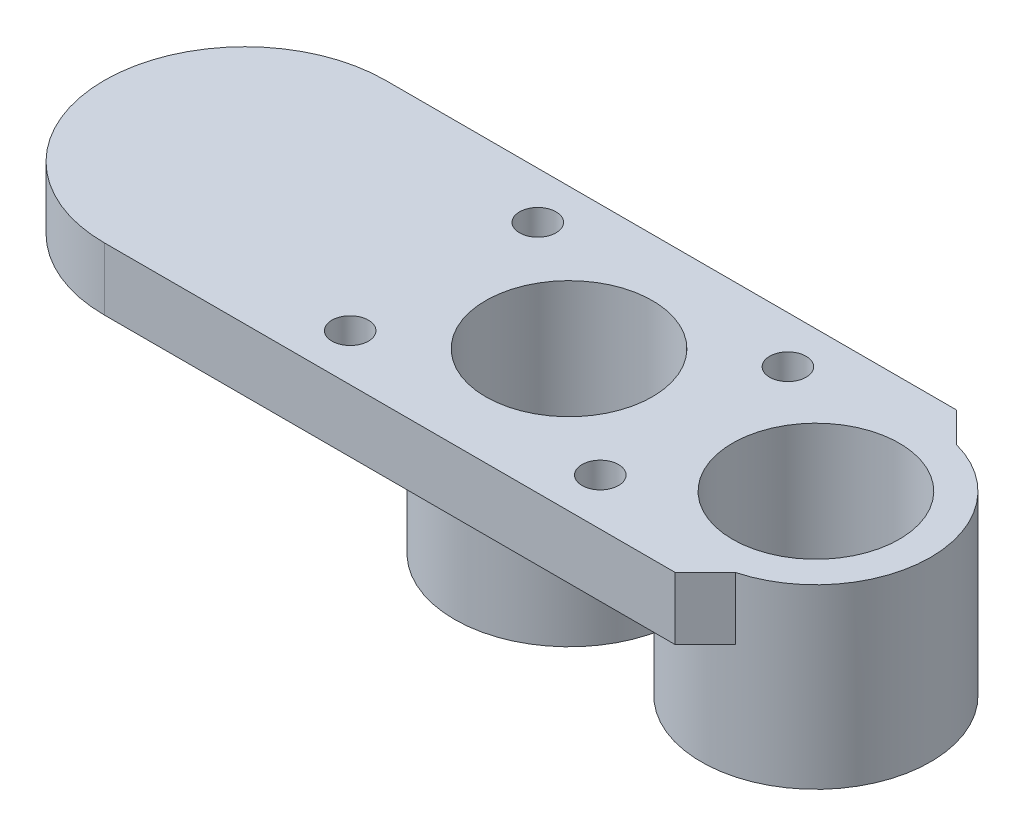
SolidWorks part; units mm, degrees
ref_plane "Front Plane" through (0, 0, 0) normal (0, 0, 1) x (1, 0, 0)
ref_plane "Top Plane" through (0, 0, 0) normal (0, 1, 0) x (1, 0, 0)
ref_plane "Right Plane" through (0, 0, 0) normal (1, 0, 0) x (0, 0, -1)
sketch "Sketch1" plane through (0, 0, 0) normal (0, 1, 0) x (1, 0, 0)
  line L1 (-31.1, 13.5) -> (23.69, 13.5)
  line L2 (-31.1, 13.5) -> (-31.1, -13.5)
  line L3 (-31.1, -13.5) -> (23.69, -13.5)
  line L4 (23.69, 13.5) -> (23.69, -13.5)
  circle A0 centre (23.69, 0) radius 11
  circle A1 centre (-31.1, 0) radius 10.5
  circle A2 centre (12, 9) radius 1.75
  circle A3 centre (23.69, 0) radius 5
  circle A4 centre (0, 0) radius 5
  circle A5 centre (12, -9) radius 1.75
  circle A6 centre (-12, -9) radius 1.75
  circle A7 centre (-12, 9) radius 1.75
  dimension "D5" = 22
  dimension "D6" = 21
  dimension "D7" = 3.5
  dimension "D10" = 10
  dimension "D11" = 10
  dimension "D12" = 3.5
  dimension "D15" = 3.5
  dimension "D17" = 3.5
  dimension "D1" = 31.1
  dimension "D2" = 23.69
  dimension "D3" = 27
  dimension "D4" = 13.5
  dimension "D8" = 12
  dimension "D9" = 9
  dimension "D13" = 12
  dimension "D14" = 9
  dimension "D16" = 12
extrude "Boss-Extrude1" add sketch "Sketch1" along normal blind 6 contours A1 L2 L3 L4 A0 L1 A7 A6 A5 A4 A2 | A3 L4 A0 | A3 L4 A0 region at (-3.705, 0, -12.8892) region at (29.0217, 0, 0) region at (18.3583, 0, 0)
sketch "Sketch2" plane through (0, 0, 0) normal (0, -1, 0) x (1, 0, 0)
  circle A0 centre (12, -9) radius 1.75 construction
  circle A1 centre (12, 9) radius 1.75 construction
  circle A2 centre (-12, 9) radius 1.75 construction
  circle A3 centre (-12, -9) radius 1.75 construction
  circle A4 centre (12, -9) radius 1.75
  circle A5 centre (12, 9) radius 1.75
  circle A6 centre (-12, 9) radius 1.75
  circle A7 centre (-12, -9) radius 1.75
  circle A8 centre (-12, -9) radius 3
  circle A9 centre (-12, 9) radius 3
  circle A10 centre (12, 9) radius 3
  circle A11 centre (12, -9) radius 3
  dimension "D1" = 6
  dimension "D2" = 6
  dimension "D3" = 6
  dimension "D4" = 6
extrude "Cut-Extrude1" cut sketch "Sketch2" against normal blind 3
sketch "Sketch3" plane through (0, 6, 0) normal (0, 1, 0) x (1, 0, 0)
  circle A0 centre (0, 0) radius 8
  circle A1 centre (0, 0) radius 5 construction
  circle A2 centre (23.69, 0) radius 5 construction
  circle A3 centre (0, 0) radius 5
  circle A4 centre (23.69, 0) radius 5
  circle A5 centre (23.69, 0) radius 8
  dimension "D1" = 16
  dimension "D2" = 16
extrude "Cut-Extrude2" cut sketch "Sketch3" against normal blind 3
sketch "Sketch5" plane through (0, 0, 0) normal (0, 1, 0) x (1, 0, 0)
  arc A0 (-31.1, -10.5) -> (-31.1, 10.5) centre (-31.1, 0) ccw construction
  arc A1 (-31.1, -10.5) -> (-31.1, 10.5) centre (-31.1, 0) ccw
  circle A2 centre (-31.1, 0) radius 13.5
extrude "Boss-Extrude2" add sketch "Sketch5" along normal blind 6 contours A2 region at (-31.1, 0, 0)
sketch "Sketch6" plane through (0, 6, 0) normal (0, 1, 0) x (1, 0, 0)
  arc A0 (23.69, -11) -> (23.69, 11) centre (23.69, 0) ccw construction
  circle A1 centre (23.69, 0) radius 8 construction
  circle A2 centre (0, 0) radius 8 construction
  arc A3 (23.69, -11) -> (23.69, 11) centre (23.69, 0) ccw
  circle A4 centre (23.69, 0) radius 8
  circle A5 centre (0, 0) radius 8
  circle A6 centre (0, 0) radius 11
  circle A7 centre (23.69, 0) radius 11
  circle M8 centre (0, 0) radius 8
  circle M9 centre (23.69, 0) radius 8
  dimension "D1" = 22
extrude "Cut-Extrude3" cut sketch "Sketch6" against normal through all both and the other way through all contours M8 | M9 region at (23.69, 6, 0) region at (0, 6, 0)
sketch "Sketch9" plane through (0, 0, 0) normal (0, 1, 0) x (1, 0, 0)
  arc A0 (23.69, -11) -> (23.69, 11) centre (23.69, 0) ccw construction
  circle A1 centre (23.69, 0) radius 8 construction
  circle A2 centre (0, 0) radius 8 construction
  arc A3 (23.69, -11) -> (23.69, 11) centre (23.69, 0) ccw
  circle A4 centre (23.69, 0) radius 8
  circle A5 centre (0, 0) radius 8
  circle A6 centre (0, 0) radius 11
  circle A7 centre (23.69, 0) radius 11
  dimension "D1" = 22
extrude "Boss-Extrude6" add sketch "Sketch9" against normal blind 8 contours A6 A5 | A3 A7 A4 region at (13.0011, 0, 0) region at (-10.6889, 0, 0)
sketch "Sketch10" plane through (0, -8, 0) normal (0, -1, 0) x (1, 0, 0)
  circle A0 centre (23.69, 0) radius 11 construction
  circle A1 centre (0, 0) radius 11 construction
  circle A2 centre (23.69, 0) radius 11
  circle A3 centre (0, 0) radius 11
  circle A4 centre (0, 0) radius 5
  circle A5 centre (23.69, 0) radius 5
  dimension "D1" = 10
  dimension "D2" = 10
extrude "Boss-Extrude7" add sketch "Sketch10" along normal blind 3
chamfer "Chamfer3" distance 2.5 angle 45 2 edges at (23.69, 3, 11) (23.69, 3, -11)
